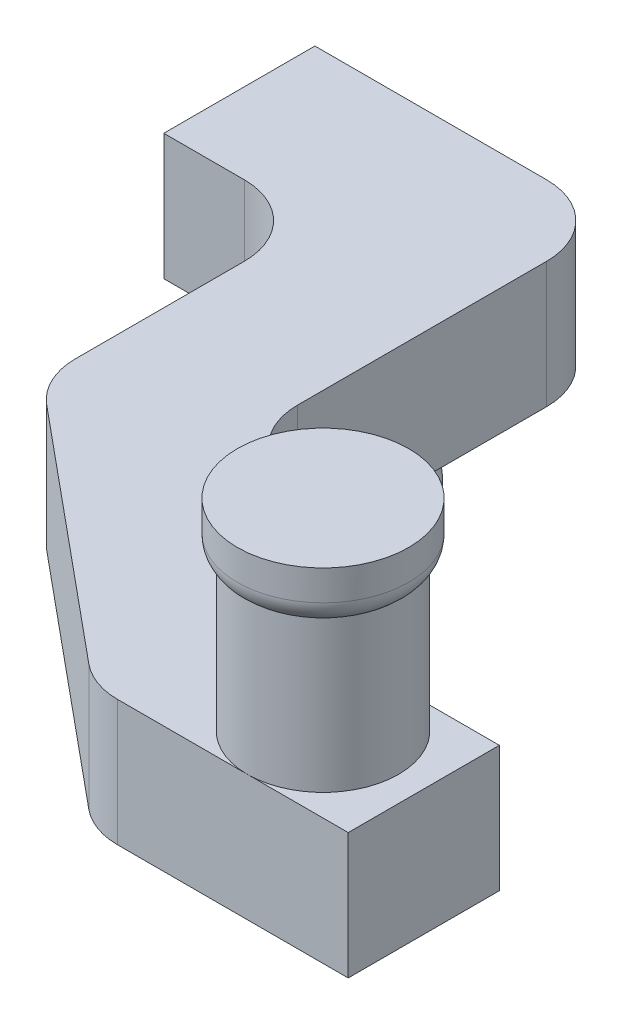
SolidWorks part; units mm, degrees
ref_plane "Front Plane" through (0, 0, 0) normal (0, 0, 1) x (1, 0, 0)
ref_plane "Top Plane" through (0, 0, 0) normal (0, 1, 0) x (1, 0, 0)
ref_plane "Right Plane" through (0, 0, 0) normal (1, 0, 0) x (0, 0, -1)
sketch "Sketch1" plane through (0, 0, 0) normal (0, 1, 0) x (1, 0, 0)
  line L0 (0, 0) -> (6, 0)
  line L1 (6, 0) -> (6, -7)
  line L2 (6, -7) -> (9.8505, -10.1896)
  line L3 (9.8505, -10.1896) -> (13.8505, -10.1896)
  line L4 (0, -3) -> (3, -3)
  line L5 (3, -3) -> (3, -8.4105)
  line L6 (3, -8.4105) -> (8.7694, -13.1896)
  line L7 (8.7694, -13.1896) -> (13.8505, -13.1896)
  line L8 (13.8505, -10.1896) -> (13.8505, -13.1896)
  line L9 (0, 0) -> (0, -3)
  dimension "D1" = 6
  dimension "D2" = 7
  dimension "D3" = 5
  dimension "D4" = 4
  dimension "D5" = 3
extrude "Boss-Extrude1" add sketch "Sketch1" along normal blind 2.5
fillet "Fillet1" radius 1.4 5 edges at (6, 1.25, 7) (3, 1.25, 8.4105) (3, 1.25, 3) (6, 1.25, 0) (8.7694, 1.25, 13.1896)
sketch "Sketch2" plane through (0, 2.5, 0) normal (0, 1, 0) x (1, 0, 0)
  line L0 (13.8505, -10.1896) -> (9.8505, -10.1896) construction
  line L1 (13.8505, -13.1896) -> (13.8505, -10.1896) construction
  circle A0 centre (11.8505, -11.6896) radius 1.5
  dimension "D1" = 1.5
  dimension "D2" = 2
extrude "Boss-Extrude2" add sketch "Sketch2" along normal blind 3
sketch "Sketch3" plane through (0, 5.5, 0) normal (0, 1, 0) x (1, 0, 0)
  circle A0 centre (11.8505, -11.6896) radius 1.7
extrude "Boss-Extrude3" add sketch "Sketch3" along normal blind 1
fillet "Fillet2" radius 0.5 1 edges at (11.8505, 5.5, 13.3896)
sketch "Sketch4" plane through (0, 0, 0) normal (0, -1, 0) x (-1, 0, 0)
  circle A0 centre (-1.5563, -1.4668) radius 1.5
extrude "Boss-Extrude4" add sketch "Sketch4" along normal blind 3
sketch "Sketch5" plane through (0, -3, 0) normal (0, -1, 0) x (1, 0, 0)
  circle A0 centre (1.5536, 1.4529) radius 1.72
extrude "Boss-Extrude5" add sketch "Sketch5" along normal blind 1
fillet "Fillet3" radius 0.5 1 edges at (1.5536, -3, -0.2671)
